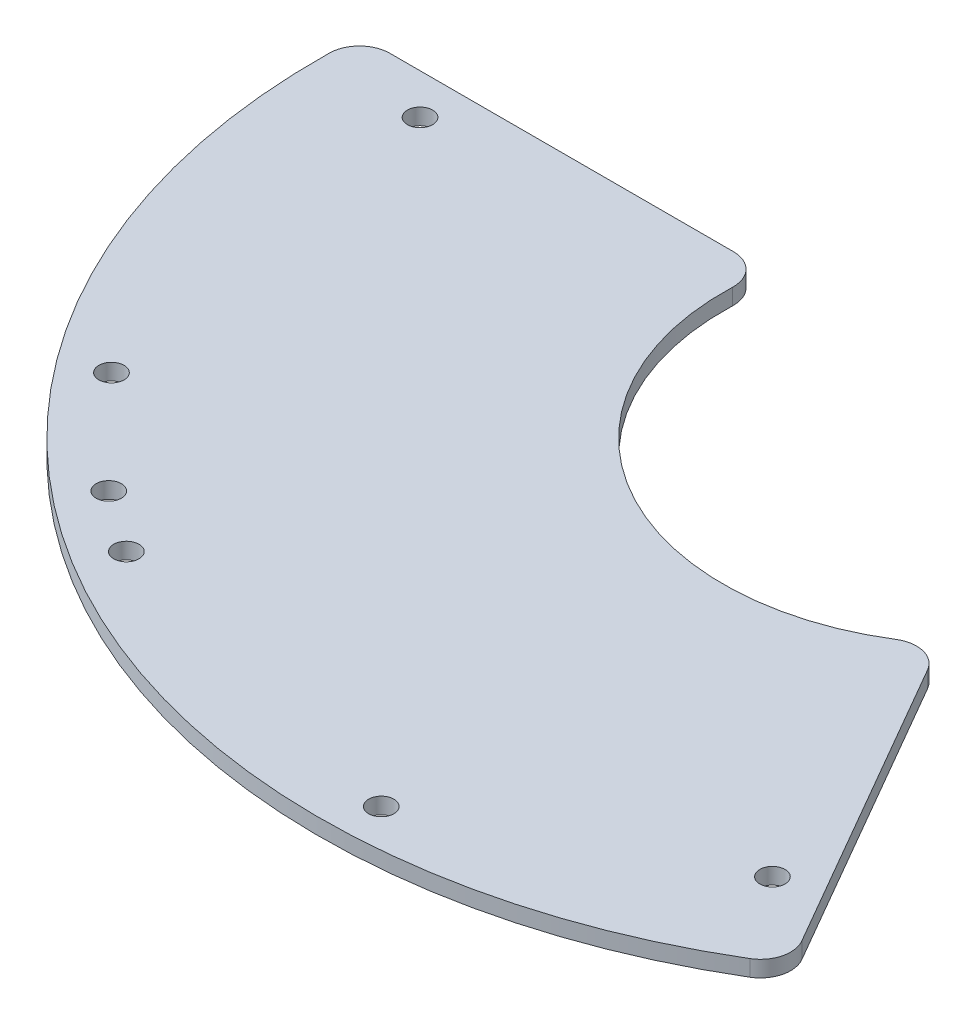
SolidWorks part; units mm, degrees
material "Thornel VCB-20 Carbon Cloth"
ref_plane "Front Plane" through (0, 0, 0) normal (0, 0, 1) x (1, 0, 0)
ref_plane "Top Plane" through (0, 0, 0) normal (0, 1, 0) x (1, 0, 0)
ref_plane "Right Plane" through (0, 0, 0) normal (1, 0, 0) x (0, 0, -1)
sketch "Sketch1" plane through (0, 0, 0) normal (0, 1, 0) x (1, 0, 0)
  line L1 (0, 0) -> (32.5, -56.2917) construction
  line L2 (0, 0) -> (-65, 0) construction
  line L3 (-64.8768, 4) -> (-24.6779, 4)
  line L4 (35.9025, -54.185) -> (15.8031, -19.3717)
  line L5 (0, 0) -> (2.1289, -60.9628) construction
  line L6 (0, 0) -> (-32.3251, -51.7309) construction
  line L7 (0, 0) -> (-48.3946, -37.1344) construction
  line L8 (-38.3885, -47.4059) -> (0, 0) construction
  arc A0 (-64.8768, 4) -> (35.9025, -54.185) centre (0, 0) ccw
  arc A1 (-24.6779, 4) -> (15.8031, -19.3717) centre (0, 0) ccw
  circle A2 centre (0, 0) radius 55 construction
  circle A3 centre (-55, 0) radius 1.25
  circle A4 centre (27.5, -47.6314) radius 1.25
  circle A5 centre (0, 0) radius 61 construction
  circle A6 centre (2.1289, -60.9628) radius 1.25
  circle A7 centre (-32.3251, -51.7309) radius 1.25
  circle A8 centre (-38.3885, -47.4059) radius 1.25
  circle A9 centre (-48.3946, -37.1344) radius 1.25
  point P4 (-58.185, -28.9743)
  point P5 (-58.185, -28.9743)
  dimension "D1" = 50
  dimension "D2" = 130
  dimension "D3" = 110
  dimension "D7" = 2.5
  dimension "D5" = 4
  dimension "D6" = 4
  dimension "D8" = 4
  dimension "D9" = 28
  dimension "D10" = 62
  dimension "D11" = 69
  dimension "D12" = 82.5
  dimension "D4" = 120
extrude "Boss-Extrude1" add sketch "Sketch1" along normal mid plane 1.6
fillet "Fillet1" radius 3 4 edges at (-64.8768, 0, -4) (-24.6779, 0, -4) (35.9025, 0, 54.185) (15.8031, 0, 19.3717)
equation "\"pcb_mount_circle_diameter\"= 110mm"
equation "\"outer_diameter\" = 130mm"
equation "\"inner_diameter\"= 50mm"
equation "\"D1@Sketch1\"=\"inner_diameter\""
equation "\"D2@Sketch1\"=\"outer_diameter\""
equation "\"D3@Sketch1\"=\"pcb_mount_circle_diameter\""
equation "\"D6@Sketch1\"=\"D5@Sketch1\""
